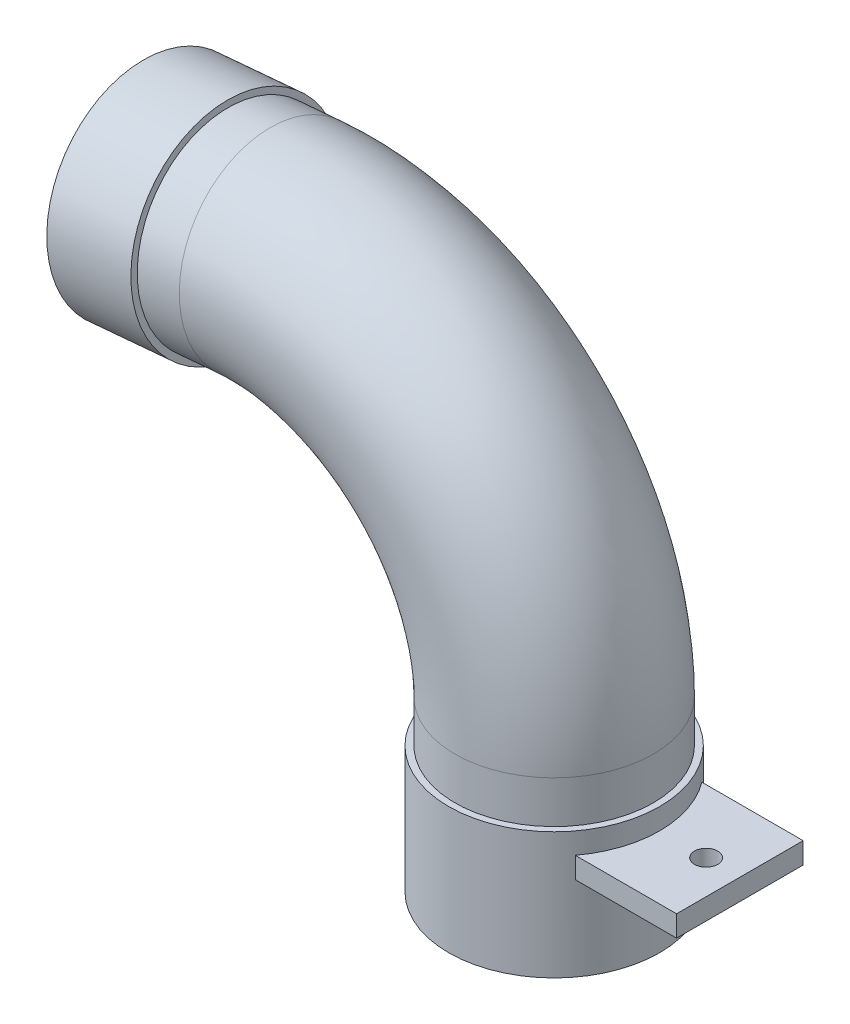
SolidWorks part; units mm, degrees
ref_plane "前视基准面" through (0, 0, 0) normal (0, 0, 1) x (1, 0, 0)
ref_plane "上视基准面" through (0, 0, 0) normal (0, 1, 0) x (1, 0, 0)
ref_plane "右视基准面" through (0, 0, 0) normal (1, 0, 0) x (0, 0, -1)
sketch "草图1" plane through (0, 0, 0) normal (0, 1, 0) x (1, 0, 0)
  circle A0 centre (0, 0) radius 22
  circle A1 centre (0, 0) radius 23.5
  dimension "D1" = 44
  dimension "D2" = 47
sketch "草图2" plane through (0, 0, 0) normal (0, 0, 1) x (1, 0, 0)
  line L0 (0, 0) -> (0, 20)
  line L3 (-65.2293, 79.7717) -> (-85.1532, 78.0286)
  arc A0 (-65.2293, 79.7717) -> (0, 20) centre (-60, 20) cw
  point P5 (0, 0)
  point P6 (0, 0)
  dimension "D2" = 85
  dimension "D3" = 60
  dimension "D1" = 20
sweep "扫描1" add profiles "草图1" path "草图2"
sketch "草图3" plane through (0, 0, 0) normal (0, -1, 0) x (1, 0, 0)
  circle A0 centre (0, 0) radius 23
  circle A1 centre (0, 0) radius 25
  dimension "D1" = 46
  dimension "D2" = 50
extrude "凸台-拉伸1" add sketch "草图3" along normal blind 20 and the other way blind 10 separate body
sketch "草图4" plane through (-77.7316, -6.8006, 0) normal (-0.9962, -0.0872, 0) x (0, 0, 1)
  circle A0 centre (0, 85.1532) radius 23
  circle A1 centre (0, 85.1532) radius 25
  dimension "D1" = 46
  dimension "D2" = 50
extrude "凸台-拉伸2" add sketch "草图4" along normal blind 10 and the other way blind 10
sketch "草图5" plane through (0, 0, 0) normal (0, -1, 0) x (-1, 0, 0)
  line L0 (-44, 15) -> (-20, 15)
  line L2 (-20, -15) -> (-44, -15)
  line L3 (-44, -15) -> (-44, 15)
  line L4 (-44, 0) -> (0, 0) construction
  circle A0 centre (-36, 0) radius 2.75
  arc A1 (-20, 15) -> (-20, -15) centre (0, 0) ccw
  circle A2 centre (0, 0) radius 25 construction
  point P12 (0, 0)
  point P13 (0, 0)
  dimension "D2" = 5.5
  dimension "D1" = 36
  dimension "D3" = 30
  dimension "D4" = 8
extrude "凸台-拉伸3" add sketch "草图5" against normal blind 5
